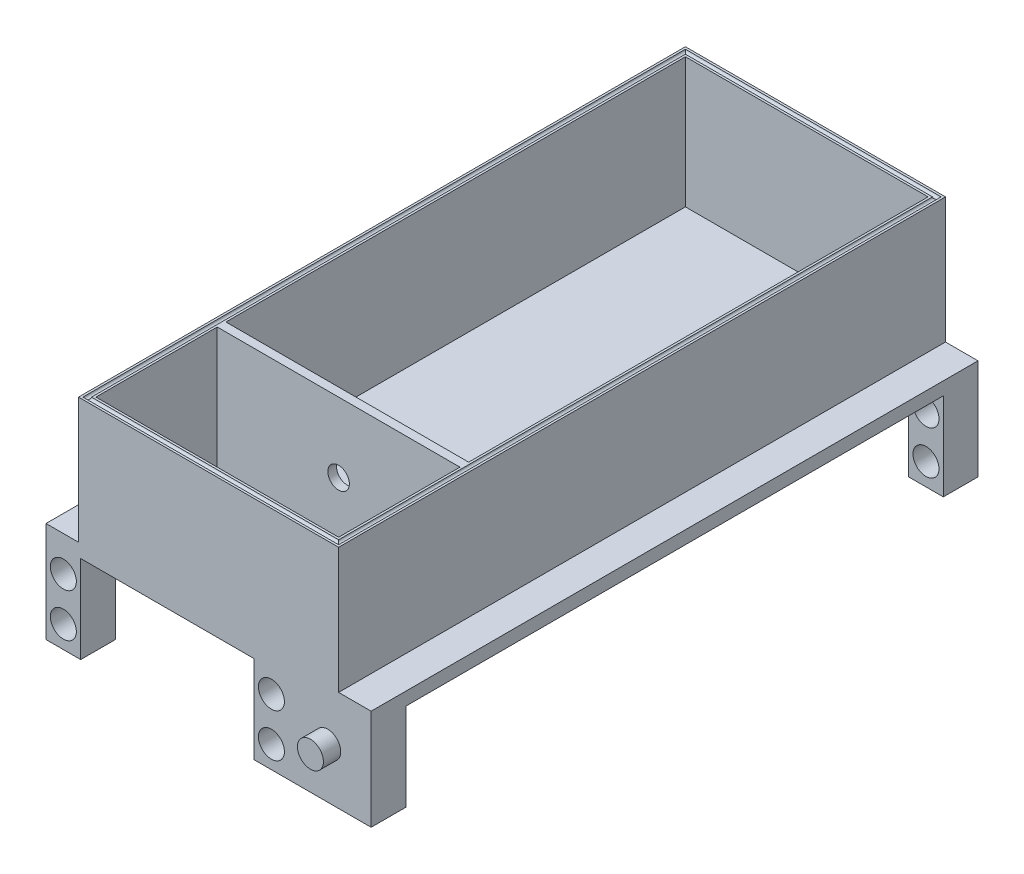
SolidWorks part; units mm, degrees
ref_plane "Front Plane" through (0, 0, 0) normal (0, 0, 1) x (1, 0, 0)
ref_plane "Top Plane" through (0, 0, 0) normal (0, 1, 0) x (1, 0, 0)
ref_plane "Right Plane" through (0, 0, 0) normal (1, 0, 0) x (0, 0, -1)
sketch "Sketch1" plane through (0, 0, 0) normal (0, 1, 0) x (1, 0, 0)
  line L1 (-30, 55) -> (30, 55)
  line L2 (-30, 55) -> (-30, -55)
  line L3 (-30, -55) -> (30, -55)
  line L4 (30, 55) -> (30, -55)
  line L5 (-30, 55) -> (30, -55) construction
  line L6 (-30, -55) -> (30, 55) construction
  point P0 (0, 0)
  dimension "D1" = 110
  dimension "D2" = 60
extrude "Boss-Extrude1" add sketch "Sketch1" along normal blind 2
sketch "Sketch2" plane through (0, 2, 0) normal (0, 1, 0) x (1, 0, 0)
  line L0 (-28, 53) -> (-28, -53)
  line L1 (-28, -53) -> (28, -53)
  line L2 (28, -53) -> (28, 53)
  line L3 (28, 53) -> (-28, 53)
  line L4 (30, -55) -> (30, 55)
  line L5 (30, 55) -> (-30, 55)
  line L6 (-30, 55) -> (-30, -55)
  line L7 (-30, -55) -> (30, -55)
  line L8 (30, -55) -> (30, 55)
  line L9 (30, 55) -> (-30, 55)
  line L10 (-30, 55) -> (-30, -55)
  line L11 (-30, -55) -> (30, -55)
  dimension "D1" = 0
  dimension "D2" = 2
extrude "Boss-Extrude2" add sketch "Sketch2" along normal blind 30
sketch "Sketch3" plane through (0, 0, 0) normal (0, 1, 0) x (1, 0, 0)
  line L0 (-30, -55) -> (30, -55) construction
  line L1 (-30, -55) -> (30, -55)
  line L2 (-30, -55) -> (-30, -85)
  line L3 (-30, -85) -> (30, -85)
  line L4 (30, -55) -> (30, -85)
  line L5 (30, -55) -> (30, 55) construction
  line L6 (-30, 55) -> (-30, -55) construction
  dimension "D2" = 30
extrude "Boss-Extrude3" add sketch "Sketch3" along normal blind 2
sketch "Sketch4" plane through (0, 2, 0) normal (0, 1, 0) x (1, 0, 0)
  line L4 (-28, -55) -> (-30, -55)
  line L8 (-28, -57) -> (-28, -83)
  line L9 (-28, -83) -> (28, -83)
  line L10 (28, -83) -> (28, -57)
  line L11 (28, -57) -> (-28, -57)
  line L12 (-28, -55) -> (-28, -83)
  line L13 (-28, -83) -> (28, -83)
  line L14 (28, -83) -> (28, -55)
  line L16 (-30, -55) -> (-30, -85)
  line L17 (-30, -85) -> (30, -85)
  line L18 (30, -85) -> (30, -55)
  line L19 (30, -55) -> (-30, -55)
  line L20 (-30, -55) -> (-30, -85)
  line L21 (-30, -85) -> (30, -85)
  line L22 (30, -85) -> (30, -55)
  line L23 (30, -55) -> (28, -55)
  dimension "D1" = 2
  dimension "D2" = 0
extrude "Boss-Extrude4" add sketch "Sketch4" along normal blind 30
sketch "Sketch5" plane through (0, 0, 55) normal (0, 0, 1) x (1, 0, 0)
  circle A0 centre (0, 15.8909) radius 2.4868
extrude "Cut-Extrude1" cut sketch "Sketch5" against normal blind 30
sketch "Sketch6" plane through (0, 32, 0) normal (0, 1, 0) x (1, 0, 0)
  line L17 (-29, 54) -> (-29, -84)
  line L18 (-29, -84) -> (29, -84)
  line L19 (29, -84) -> (29, 54)
  line L22 (29, 54) -> (-29, 54)
  line L25 (-29, 54) -> (-29, -84)
  line L26 (-29, -84) -> (29, -84)
  line L27 (29, -84) -> (29, 54)
  line L30 (29, 54) -> (-29, 54)
  dimension "D1" = 1
sweep "Cut-Sweep1" cut path "Sketch6" circular profile diameter 1 parameters "D3"=1
sketch "Sketch43" plane through (0, 0, 0) normal (0, -1, 0) x (1, 0, 0)
  line L11 (30, -55) -> (37.5, -55)
  line L12 (37.5, -55) -> (37.5, 85)
  line L13 (37.5, 85) -> (30, 85)
  line L14 (-30, -55) -> (-37.5, -55)
  line L15 (-37.5, -55) -> (-37.5, 85)
  line L16 (-37.5, 85) -> (-30, 85)
  line L18 (-30, 55) -> (-30, -55)
  line L19 (-30, 55) -> (-30, 85)
  line L21 (30, -55) -> (30, 85)
  dimension "D1" = 7.5
  dimension "D2" = 7.5
extrude "Boss-Extrude7" add sketch "Sketch43" against normal blind 3 contours L13 L21 L11 L12 | L16 L19 L18 L14 L15
sketch "Sketch55" plane through (0, 0, 0) normal (0, -1, 0) x (1, 0, 0)
  line L0 (-37.5, 85) -> (37.5, 85) construction
  line L1 (-37.5, 85) -> (-29.5, 85)
  line L2 (-37.5, 85) -> (-37.5, 77)
  line L3 (-37.5, 77) -> (-29.5, 77)
  line L4 (-29.5, 85) -> (-29.5, 77)
  line L5 (10.5, 85) -> (37.5, 85)
  line L6 (10.5, 85) -> (10.5, 77)
  line L7 (10.5, 77) -> (37.5, 77)
  line L8 (37.5, 85) -> (37.5, 77)
  line L9 (37.5, -55) -> (-37.5, -55) construction
  line L10 (37.5, -55) -> (29.5, -55)
  line L11 (37.5, -55) -> (37.5, -47)
  line L12 (37.5, -47) -> (29.5, -47)
  line L13 (29.5, -55) -> (29.5, -47)
  line L14 (-10.5, -55) -> (-37.5, -55)
  line L15 (-10.5, -55) -> (-10.5, -47)
  line L16 (-10.5, -47) -> (-37.5, -47)
  line L17 (-37.5, -55) -> (-37.5, -47)
  line L18 (37.5, -55) -> (37.5, 85) construction
  line L19 (-37.5, -55) -> (-37.5, 85) construction
  dimension "D1" = 8
  dimension "D2" = 8
  dimension "D3" = 8
  dimension "D5" = 40
  dimension "D6" = 8
  dimension "D7" = 8
  dimension "D8" = 8
  dimension "D10" = 40
extrude "Boss-Extrude10" add sketch "Sketch55" along normal blind 20.2
sketch "Sketch56" plane through (0, 0, 85) normal (0, 0, 1) x (1, 0, 0)
  line L0 (-29.5, 0) -> (-37.5, 0) construction
  line L1 (-9.5, 0) -> (-9.5, -17.0658) construction
  line L2 (-29.5, -20.2) -> (-37.5, -20.2) construction
  line L3 (-33.5, -15.1) -> (-33.5, -20.2) construction
  line L4 (-33.5, -15.1) -> (-33.5, -5.1) construction
  line L5 (-33.5, -5.1) -> (-33.5, 0) construction
  line L6 (-29.5, 0) -> (10.5, 0) construction
  circle A0 centre (-33.5, -15.1) radius 3
  circle A1 centre (-33.5, -5.1) radius 3
  circle A2 centre (14.5, -15.1) radius 3
  circle A3 centre (14.5, -5.1) radius 3
  dimension "D1" = 6
  dimension "D2" = 6
  dimension "D3" = 10
extrude "Cut-Extrude3" cut sketch "Sketch56" against normal blind 20.2
sketch "Sketch59" plane through (0, 0, -55) normal (0, 0, -1) x (-1, 0, 0)
  line L0 (-29.5, 0) -> (-37.5, 0) construction
  line L1 (-9.5, 0) -> (-9.5, -20.2) construction
  line L2 (-29.5, -20.2) -> (-37.5, -20.2) construction
  line L3 (-33.5, 0) -> (-33.5, -5.1) construction
  line L4 (-33.5, -20.2) -> (-33.5, -15.1) construction
  line L5 (-29.5, 0) -> (10.5, 0) construction
  circle A0 centre (-33.5, -15.1) radius 3
  circle A1 centre (-33.5, -5.1) radius 3
  circle A2 centre (14.5, -5.1) radius 3
  circle A3 centre (14.5, -15.1) radius 3
  dimension "D2" = 6
  dimension "D3" = 6
  dimension "D1" = 10
extrude "Cut-Extrude4" cut sketch "Sketch59" against normal blind 20.2
sketch "Sketch60" plane through (0, 0, -55) normal (0, 0, -1) x (-1, 0, 0)
  line L0 (37.5, 3) -> (37.5, -20.2) construction
  line L1 (30, 3) -> (-30, 3) construction
  line L2 (27.5, 3) -> (27.5, -8.6) construction
  line L3 (27.5, -8.6) -> (27.5, -20.2) construction
  line L4 (37.5, -20.2) -> (10.5, -20.2) construction
  circle A0 centre (27.5, -8.6) radius 3
  dimension "D1" = 6
  dimension "D2" = 10
extrude "Boss-Extrude11" add sketch "Sketch60" along normal blind 4
sketch "Sketch61" plane through (0, 0, 85) normal (0, 0, 1) x (1, 0, 0)
  line L0 (30, 3) -> (-30, 3) construction
  line L1 (27.5, -8.6) -> (27.5, 3) construction
  line L2 (27.5, -8.6) -> (27.5, -20.2) construction
  line L3 (37.5, -20.2) -> (10.5, -20.2) construction
  line L4 (37.5, 3) -> (37.5, -20.2) construction
  circle A0 centre (27.5, -8.6) radius 3
  dimension "D1" = 6
  dimension "D2" = 10
extrude "Boss-Extrude12" add sketch "Sketch61" along normal blind 4
